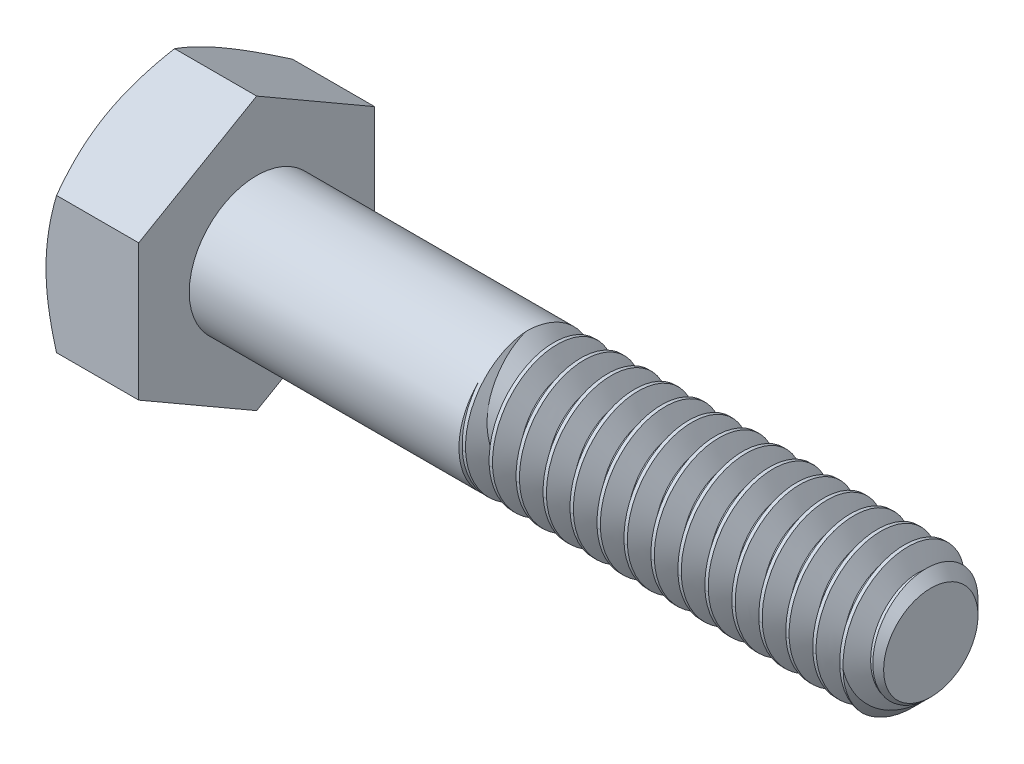
SolidWorks part; units mm, degrees
note: '?' marks a value the reader was unsure of.
ref_plane "Front Plane" through (0, 0, 0) normal (0, 0, 1) x (1, 0, 0)
ref_plane "Top Plane" through (0, 0, 0) normal (0, 1, 0) x (1, 0, 0)
ref_plane "Right Plane" through (0, 0, 0) normal (1, 0, 0) x (0, 0, -1)
sketch "Sketch1" plane through (0, 0, 0) normal (0, 0, 1) x (1, 0, 0)
  line L0 (-18.0578, 0) -> (18.0578, 0) construction
  line L1 (18.0578, 3.175) -> (18.0578, -3.175) construction
  line L2 (-13.6922, 5.5562) -> (-13.6922, -5.5562) construction
  line L3 (-18.0578, 5.5562) -> (-18.0578, -5.5562) construction
  point P9 (-13.6922, 0)
  point P10 (13.6128, -3.175)
  dimension "D1" = 4.445
  dimension "Screw Dia" = 6.35
  dimension "Hex" = 11.1125
  dimension "Head Ht" = 4.3656
  dimension "Screw Lenght" = 31.75
ref_plane "Plane2" through (18.0578, 0, 0) normal (1, 0, 0) x (0, 0, -1)
sketch "Sketch5" plane through (18.0578, 0, 0) normal (1, 0, 0) x (0, 0, -1)
  circle A0 centre (0, 0) radius 3.175
extrude "Boss-Extrude3" add sketch "Sketch5" against normal up to vertex (31.75 mm away) up to point (-13.6922, 0, 0)
sketch "Sketch9" plane through (18.0578, 0, 0) normal (1, 0, 0) x (0, 0, -1)
  circle A1 centre (0, 0) radius 3.175
  circle A2 centre (0, 0) radius 3.175
  dimension "D1" = 0
curve "Helix/Spiral1" pitch 1.27 height 20.32 turns 16 parameters "Pitch"=1.27
chamfer "Chamfer1" distance 0.9525 angle 45 1 edges at (18.0578, 0, -3.175)
sketch "Sketch10" plane through (0, 0, 0) normal (0, 0, 1) x (1, 0, 0)
  line L0 (18.0578, 3.175) -> (18.5341, 2.3501)
  line L1 (18.5341, 2.3501) -> (18.6928, 2.3501)
  line L2 (18.6928, 2.3501) -> (19.1691, 3.175)
  line L3 (18.0578, 3.175) -> (19.1691, 3.175)
  line L4 (18.6134, 3.175) -> (18.6134, 2.3501) construction
  line L5 (18.2959, 2.7626) -> (18.9309, 2.7626) construction
  dimension "D1" = 60
  dimension "D2" = 0.1588
  dimension "D3" = 0.635
sweep "Cut-Sweep1" cut profiles "Sketch10" path "Helix/Spiral1"
sketch "Sketch11" plane through (0, 0, 0) normal (0, 0, 1) x (1, 0, 0)
  line L0 (-13.6922, 3.175) -> (-13.6922, 0)
  line L1 (-13.6922, 0) -> (2.1828, 0)
  line L3 (2.1828, 0) -> (-0.9922, 3.175)
  line L4 (-13.6922, 3.175) -> (-0.9922, 3.175)
  dimension "D1" = 45
  dimension "MIn Thread" = 19.05
revolve "Revolve1" add sketch "Sketch11" angle 360 about L1
sketch "Sketch6" plane through (-13.6922, 0, 0) normal (-1, 0, 0) x (0, 0, 1)
  line L0 (0, 5.5562) -> (0, -5.5562) construction
  line L1 (5.5563, 3.2079) -> (0, 6.4158)
  line L2 (0, 6.4158) -> (-5.5563, 3.2079)
  line L3 (-5.5563, 3.2079) -> (-5.5563, -3.2079)
  line L4 (-5.5563, -3.2079) -> (0, -6.4158)
  line L5 (0, -6.4158) -> (5.5563, -3.2079)
  line L6 (5.5563, -3.2079) -> (5.5563, 3.2079)
  circle A0 centre (0, 0) radius 5.5562 construction
extrude "Boss-Extrude4" add sketch "Sketch6" along normal up to vertex (4.3656 mm away) up to point (-18.0578, -5.5562, 0)
sketch "Sketch7" plane through (-18.0578, 0, 0) normal (-1, 0, 0) x (0, 0, 1)
  circle A0 centre (0, 0) radius 5.5562 construction
  circle A1 centre (0, 0) radius 5.5562
sketch "Sketch8" plane through (-18.0578, 0, 0) normal (-1, 0, 0) x (0, 0, 1)
  circle A0 centre (0, 0) radius 5.5562 construction
  circle A1 centre (0, 0) radius 5.5562
extrude "Cut-Extrude3" cut sketch "Sketch8" against normal through all draft 60 flip side to cut
ref_axis "Axis1" through (-22.2204, 0, 0) along (1, 0, 0)?
equation "\"D2@Sketch10\" = \"Pitch@Helix/Spiral1\"*.125"
equation "\"D3@Sketch10\" = \"Pitch@Helix/Spiral1\"*.5"
equation "\"D3@Helix/Spiral1\" = \"MIn Thread@Sketch11\"+\"Pitch@Helix/Spiral1\""
equation "\"D1@Chamfer1\" = \"Pitch@Helix/Spiral1\"*.75"
equation "\"D1@Sketch1\" = \"Pitch@Helix/Spiral1\"*3.5"
